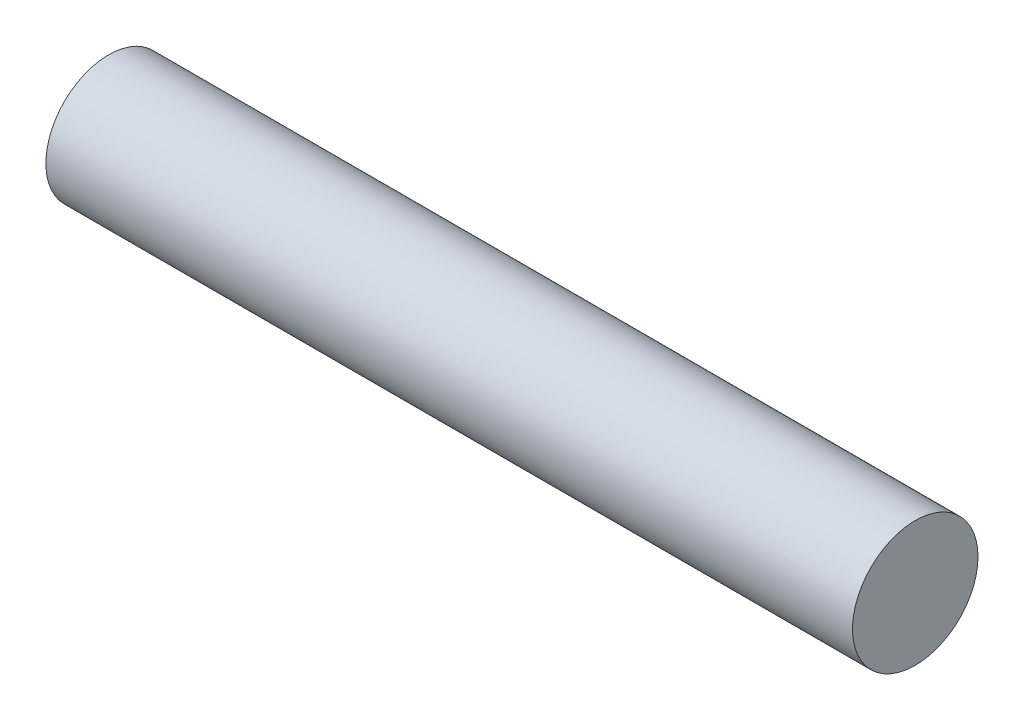
SolidWorks part; units mm, degrees
ref_plane "Front Plane" through (0, 0, 0) normal (0, 0, 1) x (1, 0, 0)
ref_plane "Top Plane" through (0, 0, 0) normal (0, 1, 0) x (1, 0, 0)
ref_plane "Right Plane" through (0, 0, 0) normal (1, 0, 0) x (0, 0, -1)
sketch "Sketch1" plane through (0, 0, 0) normal (1, 0, 0) x (0, 0, -1)
  circle A0 centre (0, 0) radius 3.556
  dimension "D1" = 7.112
extrude "Boss-Extrude1" add sketch "Sketch1" along normal mid plane 45.72
ref_axis "Axis1" through (-24.8664, 0, 0) along (1, 0, 0)
